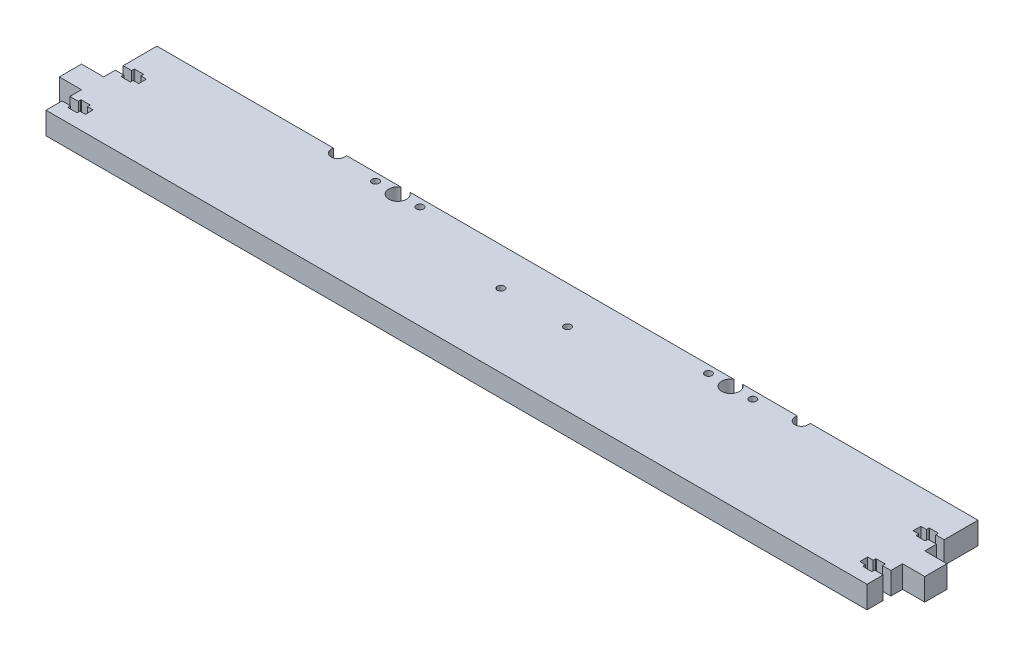
SolidWorks part; units mm, degrees
ref_plane "Front Plane" through (0, 0, 0) normal (0, 0, 1) x (1, 0, 0)
ref_plane "Top Plane" through (0, 0, 0) normal (0, 1, 0) x (1, 0, 0)
ref_plane "Right Plane" through (0, 0, 0) normal (1, 0, 0) x (0, 0, -1)
sketch "Sketch1" plane through (0, 0, 0) normal (0, 1, 0) x (1, 0, 0)
  line L0 (0, 25) -> (0, -25)
  line L1 (-185, 25) -> (0, 25)
  line L2 (-185, 25) -> (-185, -25) construction
  line L3 (-185, -25) -> (0, -25)
  line L4 (-185, -4) -> (-195, -4) construction
  line L5 (-185, 25) -> (0, 0) construction
  line L6 (-185, -25) -> (0, 0) construction
  line L7 (-185, -9) -> (-195, -9)
  line L8 (-195, -9) -> (-195, 1)
  line L9 (-195, 1) -> (-185, 1)
  line L10 (-185, 1) -> (-185, 25)
  line L11 (-185, -9) -> (-185, -25)
  line L47 (0, -25) -> (0, 25) construction
  line L89 (0, -25) -> (0, 25) construction
  point P0 (0, 0)
  dimension "D1" = 185
  dimension "D25" = 25
  dimension "D4" = 50
  dimension "D3" = 21
  dimension "D5" = 10
  dimension "D6" = 10
  dimension "D7" = 5
extrude "MainBody" add sketch "Sketch1" along normal blind 10 contours L3 region at (-93.5428, 0, 0.0428)
sketch "Sketch5" plane through (0, 10, 0) normal (0, 1, 0) x (1, 0, 0)
  line L0 (-185, 8) -> (-174.5, 8) construction
  line L1 (-185, 1) -> (-185, 25) construction
  line L2 (-185, 9.75) -> (-174.5, 9.75) construction
  line L3 (-174.5, 9.75) -> (-174.5, 6.25) construction
  line L4 (-174.5, 6.25) -> (-185, 6.25) construction
  line L5 (-185, 9.75) -> (-181.2, 9.75)
  line L6 (-181.2, 9.75) -> (-181.2, 10.75)
  line L7 (-180.95, 11) -> (-177.25, 11)
  line L8 (-177, 10.75) -> (-177, 9.75)
  line L9 (-177, 9.75) -> (-174.5, 9.75)
  line L10 (-174.5, 9.75) -> (-174.5, 6.25)
  line L11 (-185, 6.25) -> (-185, 9.75)
  line L12 (-195, -9) -> (-195, 1) construction
  line L13 (-185, 6.25) -> (-174.5, 6.25) construction
  line L14 (-177, 6.25) -> (-174.5, 6.25)
  line L15 (-177, 5.25) -> (-177, 6.25)
  line L16 (-180.95, 5) -> (-177.25, 5)
  line L17 (-181.2, 6.25) -> (-181.2, 5.25)
  line L18 (-185, 6.25) -> (-181.2, 6.25)
  line L19 (-185, 1) -> (-185, -9) construction
  line L20 (-195, -4) -> (-185, -4) construction
  line L21 (-195, -9) -> (-195, 1) construction
  line L22 (-185, -14.25) -> (-174.5, -14.25) construction
  line L23 (-174.5, -14.25) -> (-185, -14.25) construction
  line L24 (-174.5, -17.75) -> (-174.5, -14.25) construction
  line L25 (-185, -17.75) -> (-174.5, -17.75) construction
  line L26 (-185, -16) -> (-174.5, -16) construction
  line L27 (-185, -14.25) -> (-181.2, -14.25)
  line L28 (-181.2, -14.25) -> (-181.2, -13.25)
  line L29 (-180.95, -13) -> (-177.25, -13)
  line L30 (-177, -13.25) -> (-177, -14.25)
  line L31 (-177, -14.25) -> (-174.5, -14.25)
  line L32 (-185, -14.25) -> (-185, -17.75)
  line L33 (-174.5, -17.75) -> (-174.5, -14.25)
  line L34 (-177, -17.75) -> (-174.5, -17.75)
  line L35 (-177, -18.75) -> (-177, -17.75)
  line L36 (-180.95, -19) -> (-177.25, -19)
  line L37 (-181.2, -17.75) -> (-181.2, -18.75)
  line L38 (-185, -17.75) -> (-181.2, -17.75)
  line L39 (-185, 6.25) -> (-174.5, 6.25) construction
  arc A0 (-177.25, 11) -> (-177, 10.75) centre (-177.25, 10.75) cw
  arc A1 (-181.2, 10.75) -> (-180.95, 11) centre (-180.95, 10.75) cw
  arc A2 (-181.2, 5.25) -> (-180.95, 5) centre (-180.95, 5.25) ccw
  arc A3 (-177.25, 5) -> (-177, 5.25) centre (-177.25, 5.25) ccw
  arc A4 (-177.25, -13) -> (-177, -13.25) centre (-177.25, -13.25) cw
  arc A5 (-181.2, -13.25) -> (-180.95, -13) centre (-180.95, -13.25) cw
  arc A6 (-181.2, -18.75) -> (-180.95, -19) centre (-180.95, -18.75) ccw
  arc A7 (-177.25, -19) -> (-177, -18.75) centre (-177.25, -18.75) ccw
  point P6 (-195, -4)
  point P17 (-177, 11)
  point P20 (-181.2, 11)
  point P29 (-181.2, 5)
  point P30 (-177, 5)
  point P61 (-177, -13)
  point P62 (-181.2, -13)
  point P63 (-181.2, -19)
  point P64 (-177, -19)
  dimension "D8" = 0.25
  dimension "D1" = 10.5
  dimension "D2" = 1.75
  dimension "D4" = 4.2
  dimension "D5" = 8
  dimension "D6" = 3
  dimension "D7" = 12
extrude "ScrewCutouts" cut sketch "Sketch5" against normal through all
mirror "Mirror1" about plane through (0, 0, 0) normal (1, 0, 0) of "ScrewCutouts", "MainBody"
sketch "Sketch3" plane through (0, 10, 0) normal (0, 1, 0) x (1, 0, 0)
  line L0 (2, 25) -> (2, -25) construction
  line L1 (-185, 25) -> (185, 25) construction
  line L2 (-185, -25) -> (185, -25) construction
  line L3 (-63, 21.5) -> (-83, 21.5) construction
  line L4 (-73, 17.5) -> (-73, 25.5) construction
  line L5 (77, 17.5) -> (77, 25.5) construction
  line L6 (67, 21.5) -> (87, 21.5) construction
  circle A0 centre (-73, 21.5) radius 4
  circle A1 centre (-83, 21.5) radius 1.6
  circle A2 centre (-63, 21.5) radius 1.6
  circle A3 centre (67, 21.5) radius 1.6
  circle A4 centre (87, 21.5) radius 1.6
  circle A5 centre (77, 21.5) radius 4
  dimension "D2" = 8
  dimension "D4" = 3.2
  dimension "D1" = 3.5
  dimension "D3" = 10
  dimension "D5" = 75
  dimension "D6" = 2
extrude "RodCutouts" cut sketch "Sketch3" against normal through all
sketch "Sketch6" plane through (0, 10, 0) normal (0, 1, 0) x (1, 0, 0)
  line L0 (-73, 21.5) -> (77, 21.5) construction
  line L1 (2, 21.5) -> (2, -25) construction
  line L2 (-185, -25) -> (185, -25) construction
  line L3 (17, 8) -> (-13, 8) construction
  line L4 (-71.0635, 25) -> (75.0635, 25) construction
  circle A0 centre (-13, 8) radius 1.6
  circle A1 centre (17, 8) radius 1.6
  point P13 (2, 8)
  dimension "D1" = 3.2
  dimension "D2" = 15
  dimension "D3" = 17
extrude "Cut-Extrude1" cut sketch "Sketch6" against normal through all
sketch "Sketch7" plane through (0, 10, 0) normal (0, 1, 0) x (1, 0, 0)
  line L0 (-73, 21.5) -> (77, 21.5) construction
  line L1 (2, 21.5) -> (2, -25) construction
  line L3 (-102.5, 25) -> (-102.5, 24) construction
  line L4 (-185, 25) -> (-74.9365, 25) construction
  line L5 (-99.5, 25) -> (-99.5, 24)
  line L6 (-105.5, 25) -> (-105.5, 24)
  line L7 (106.5, 25) -> (106.5, 24) construction
  line L8 (103.5, 25) -> (103.5, 24)
  line L9 (109.5, 25) -> (109.5, 24)
  line L12 (-185, -25) -> (185, -25) construction
  arc A0 (-99.5, 25) -> (-105.5, 25) centre (-102.5, 25) ccw
  arc A1 (-105.5, 24) -> (-99.5, 24) centre (-102.5, 24) ccw
  arc A2 (103.5, 25) -> (109.5, 25) centre (106.5, 25) cw
  arc A3 (109.5, 24) -> (103.5, 24) centre (106.5, 24) cw
  point P12 (-102.5, 24.5)
  point P19 (106.5, 24.5)
  dimension "D1" = 3
  dimension "D2" = 1
  dimension "D3" = 104.5
extrude "BedAdjustmentScrewCutout" cut sketch "Sketch7" against normal through all
equation "\"Y-ROD-SPACING\"=75"
equation "\"Y-BED-OFFSET\"=2"
equation "\"T-SLOT-NUT-FILLET-RADIUS\"=0.25"
equation "\"T-SLOT-SCREW-SHAFT-RADIUS\"=1.75"
equation "\"T-SLOT-SCREW-SHAFT-CUTOUT-LENGTH\"=10.5"
equation "\"T-SLOT-NUT-DEPTH\"=4.2"
equation "\"T-SLOT-NUT-WIDTH\"=3"
equation "\"T-SLOT-NUT-END-DISTANCE\"=8"
equation "\"ACRYLIC-TAB-CUTOUT-SIZE\"=\"ACRYLIC-THICKNESS\"+\"ACRYLIC-TAB-TOLERANCE\"*2"
equation "\"ACRYLIC-M3-HOLE\"=3.2"
equation "\"D1@Sketch5\"=\"T-SLOT-SCREW-SHAFT-CUTOUT-LENGTH\""
equation "\"D2@Sketch5\"=\"T-SLOT-SCREW-SHAFT-RADIUS\""
equation "\"D4@Sketch5\"=\"T-SLOT-NUT-DEPTH\""
equation "\"D5@Sketch5\"=\"T-SLOT-NUT-END-DISTANCE\""
equation "\"D6@Sketch5\"=\"T-SLOT-NUT-WIDTH\""
equation "\"D8@Sketch5\"=\"T-SLOT-NUT-FILLET-RADIUS\""
equation "\"D4@Sketch3\"=\"ACRYLIC-M3-HOLE\""
equation "\"D5@Sketch3\"=\"Y-ROD-SPACING\""
equation "\"D6@Sketch3\"=\"Y-BED-OFFSET\""
equation "\"Y-BED-ROD-INSET\"=3.5"
equation "\"D1@Sketch3\"=\"Y-BED-ROD-INSET\""
equation "\"SMOOTHROD-CAP-SCREW-DISTANCE\"=20"
equation "\"D3@Sketch3\"=\"SMOOTHROD-CAP-SCREW-DISTANCE\"/2"
equation "\"ACRYLIC-TAB-WIDTH\"=\"ACRYLIC-THICKNESS\""
equation "\"FRAME-WIDTH-INNER\"=370"
equation "\"D6@Sketch1\"=\"ACRYLIC-TAB-WIDTH\""
equation "\"D5@Sketch1\"=\"ACRYLIC-TAB-WIDTH\""
equation "\"D1@Sketch1\"=\"FRAME-WIDTH-INNER\"/2"
equation "\"X-ROD-SPACING\"=45"
equation "\"Z-ROD-SPACING\"=17.5"
equation "\"ACRYLIC-THICKNESS\"=10"
equation "\"ACRYLIC-THICKNESS2\"=4.5"
equation "\"NEMA17-HOLE-SPACING\"=31"
equation "\"NEMA17-CENTRAL-CUTOUT\"=22.5"
equation "\"Z-BRACKET-REACH\"=55"
equation "\"TOP-BRACKET-SPACING\"=40"
equation "\"SMOOTHROD-X-LENGTH\"=350"
equation "\"SMOOTHROD-Y-LENGTH\"=350"
equation "\"SMOOTHROD-Z-LENGTH\"=350"
equation "\"SMOOTHROD-TIGHTENING-HEADROOM\"=1"
equation "\"LEADSCREW-Z-LENGTH\"=300"
equation "\"SCREW-LENGTH-FRAME\"=\"ACRYLIC-THICKNESS\" + 10"
equation "\"SCREW-HEAD-RADIUS\"=6"
equation "\"PRINTED-X-SMOOTHROD-DIAMETER\"=8.2"
equation "\"PRINTED-X-SMOOTHROD-CUTOUT\"=10"
equation "\"PRINTED-X-BASE-HEIGHT\"=10"
equation "\"PRINTED-LM8UU-CUTOUT-SIZE\"=15.25"
equation "\"PRINTED-LM8UU-CUTOUT-LENGTH\"=24.5"
equation "\"PRINTED-X-IDLER-HEIGHT\"=16"
equation "\"PSU-MOUNTING-WIDTH\"=95"
equation "\"PSU-MOUNTING-HEIGHT\"=177"
equation "\"D1@MainBody\"=\"ACRYLIC-THICKNESS\""
equation "\"D7@Sketch1\"=\"ACRYLIC-TAB-WIDTH\"/2"
equation "\"D1@Sketch6\"=\"ACRYLIC-M3-HOLE\""
equation "\"Y-BELT-TO-ROD-DISTANCE\"=20"
equation "\"Y-BED-SCREW-SPACING\"=209"
equation "\"Z-ROD-INSET\"=16"
equation "\"SPOOL-HOLDER-ROD-SPACING\"=150"
equation "\"D3@Sketch7\"=\"Y-BED-SCREW-SPACING\"/2"
equation "\"Y-BED-SCREW-CUTOUT-SLOT-HEIGHT\"=1"
equation "\"D2@Sketch7\"=\"Y-BED-SCREW-CUTOUT-SLOT-HEIGHT\""
